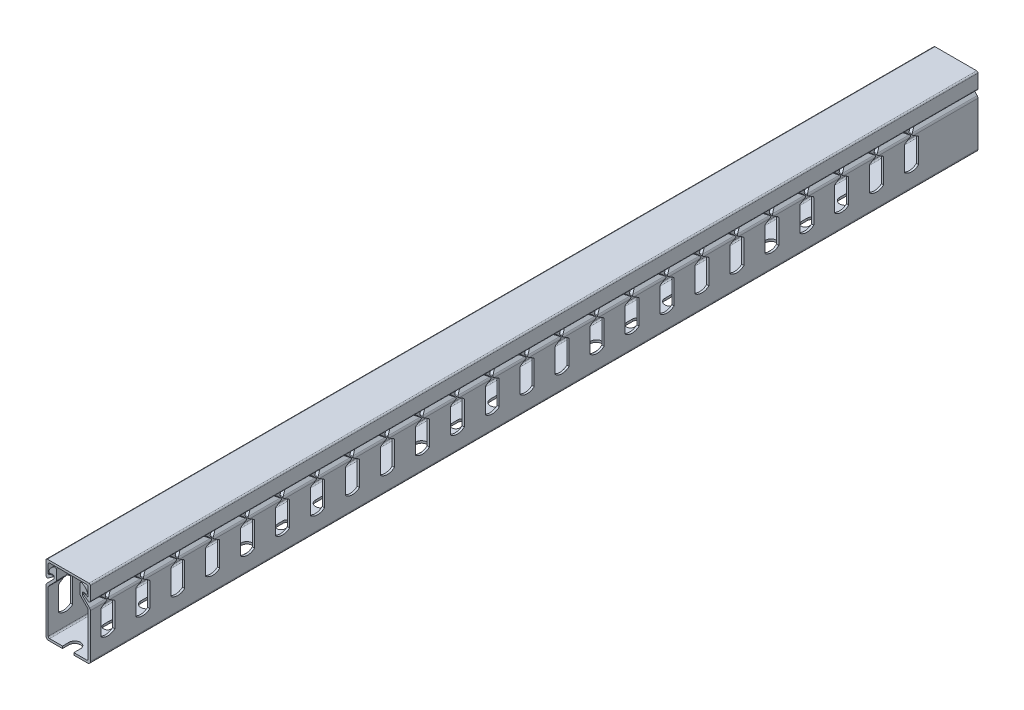
SolidWorks part; units mm, degrees
ref_plane "Front Plane" through (0, 0, 0) normal (0, 0, 1) x (1, 0, 0)
ref_plane "Top Plane" through (0, 0, 0) normal (0, 1, 0) x (1, 0, 0)
ref_plane "Right Plane" through (0, 0, 0) normal (1, 0, 0) x (0, 0, -1)
sketch "Sketch1" plane through (0, 0, 0) normal (0, 0, 1) x (1, 0, 0)
  line L0 (-12.7, 10.6985) -> (12.7, 10.6985) construction
  line L1 (12.7, -20) -> (-12.7, -20) construction
  line L2 (12.7, -20) -> (12.7, 20) construction
  line L3 (12.7, 20) -> (-12.7, 20) construction
  line L4 (-12.7, -20) -> (-12.7, 20) construction
  line L5 (0, 20) -> (0, -20) construction
  line L6 (12.7, 0) -> (-12.7, 0) construction
  line L7 (-12.7, 13.7872) -> (12.7, 13.7872) construction
  line L8 (6.8085, 20) -> (6.8085, 10.6985) construction
  line L9 (-6.8085, 20) -> (6.8085, 10.6985) construction
  line L10 (-6.8085, 20) -> (-6.8085, 10.6985) construction
  line L11 (-12.7, 18.222) -> (12.7, 18.222) construction
  line L12 (-12.7, 13.6284) -> (12.7, 13.6284) construction
  line L13 (-11.4341, 10.8542) -> (-7.685, 13.6284) construction
  line L14 (-10.1877, 13.798) -> (-6.8085, 14.3635) construction
  line L15 (12.7, 7.4) -> (6.8085, 13.4162) construction
  circle A0 centre (-11.9062, 11.4923) radius 0.7938 construction
  circle A1 centre (-10.3187, 14.5809) radius 0.7937 construction
  circle A2 centre (-7.6022, 17.4283) radius 0.7938 construction
  arc A3 (-7.9835, 18.1244) -> (-11.0321, 14.929) centre (-4.4831, 11.7329) ccw construction
  point P0 (0, 0)
  point P4 (11.43, 0)
  point P13 (0, 15.3493)
  point P16 (-11.1125, 13.7872)
  point P21 (-11.1125, 11.4923)
  point P26 (-10.3188, 13.7872)
  point P27 (-10.3188, 13.7872)
  point P28 (-11.1125, 14.5809)
  point P36 (12.7, 7.4)
  dimension "D6" = 7.2873
  dimension "Width" = 25.4
  dimension "Heigth" = 40
  dimension "Wall Thickness" = 1.27
  dimension "Cap Height" = 9.3015
  dimension "Lip Height" = 6.2128
  dimension "D1" = 13.6169
  dimension "D2" = 1.778
  dimension "Lip From Edge" = 1.5875
  dimension "D4" = 0.1588
  dimension "D5" = 36.5
  dimension "D3" = 80.5
  dimension "Shoulder Height" = 27.4
  dimension "D7" = 44.4
sketch "Sketch3" plane through (0, 0, 0) normal (1, 0, 0) x (0, 0, -1)
  line L0 (254, 0) -> (-254, 0) construction
  line L1 (-254, 20) -> (-254, -20) construction
  line L2 (-254, -20) -> (254, -20) construction
  line L3 (254, -20) -> (254, 20) construction
  line L4 (254, 20) -> (-254, 20) construction
  line L5 (-240, 20) -> (-240, 9.8437) construction
  line L6 (-240, 9.8437) -> (-243.873, 7.4) construction
  line L7 (-243.873, 7.4) -> (-244.127, 7.4) construction
  line L8 (-244.127, 7.4) -> (-248, 9.8437) construction
  line L9 (-248, 9.8437) -> (-248, 20) construction
  line L10 (-244.127, 7.4) -> (-248, 4.9563) construction
  line L11 (-248, 4.9563) -> (-248, -9.1796) construction
  line L12 (-248, -9.1796) -> (-240, -9.1796) construction
  line L13 (-240, -9.1796) -> (-240, 4.9563) construction
  line L14 (-243.873, 7.4) -> (-240, 4.9563) construction
  line L15 (-244, 7.4) -> (-244, -9.1796) construction
  line L16 (-244, 7.4) -> (-244, 20) construction
  line L17 (-248, 4.9563) -> (-240, 4.9563) construction
  line L18 (0, 7.4) -> (-243.873, 7.4) construction
  line L19 (-248, 9.8437) -> (-248, 4.9563) construction
  line L20 (-244.127, 7.4) -> (-248, 7.4) construction
  line L21 (-240, 4.9563) -> (-228, 4.9563) construction
  line L22 (-228, 4.9563) -> (-220, 4.9563) construction
  line L23 (-224, 4.9563) -> (-224, -9.1796) construction
  line L24 (-127, 20) -> (-127, -20) construction
  line L25 (127, 20) -> (127, -20) construction
  arc A0 (-248, -9.1796) -> (-240, -9.1796) centre (-244, -4.7075) ccw construction
  circle A1 centre (-244.8707, 7.4) radius 0.3969 construction
  circle A2 centre (-243.1293, 7.4) radius 0.3969 construction
  point P29 (-220, 4.9563)
  point P30 (-228, 4.9563)
  point P31 (-228, 4.9563)
  point P32 (-224, 4.9563)
  point P34 (-127, 0)
  point P39 (127, 0)
  dimension "D2" = 6
  dimension "D6" = 0.7937
  dimension "Length" = 508
  dimension "Side Cut Out Width" = 8
  dimension "D3" = 6
  dimension "D1" = 10.8204
  dimension "D4" = 64.5
  dimension "D5" = 0.254
  dimension "Cut Spacing" = 12
  dimension "Cut Center To Center" = 20
  dimension "D7" = 127
  dimension "D8" = 127
sketch "Sketch4" plane through (0, 0, 0) normal (0, 1, 0) x (1, 0, 0)
  line L0 (0, -257.75) -> (0, -250.25) construction
  line L1 (-12.7, 254) -> (12.7, 254) construction
  line L2 (-12.7, 254) -> (-12.7, -254) construction
  line L3 (-12.7, -254) -> (12.7, -254) construction
  line L4 (12.7, 254) -> (12.7, -254) construction
  line L5 (0, -254) -> (0, 254) construction
  line L6 (-12.7, 0) -> (12.7, 0) construction
  line L7 (-3.25, -257.75) -> (-3.25, -250.25) construction
  line L8 (3.25, -257.75) -> (3.25, -250.25) construction
  line L9 (0, -231.5) -> (0, -228) construction
  line L10 (-2.25, -231.5) -> (-2.25, -228) construction
  line L11 (2.25, -231.5) -> (2.25, -228) construction
  line L12 (0, -209.25) -> (0, -201.75) construction
  line L13 (-3.25, -209.25) -> (-3.25, -201.75) construction
  line L14 (3.25, -209.25) -> (3.25, -201.75) construction
  line L15 (0, -178.75) -> (0, -182.25) construction
  line L16 (2.25, -178.75) -> (2.25, -182.25) construction
  line L17 (-2.25, -178.75) -> (-2.25, -182.25) construction
  line L18 (-12.7, -127) -> (12.7, -127) construction
  line L19 (-12.7, 127) -> (12.7, 127) construction
  arc A0 (-3.25, -257.75) -> (3.25, -257.75) centre (0, -257.75) ccw construction
  arc A1 (3.25, -250.25) -> (-3.25, -250.25) centre (0, -250.25) ccw construction
  arc A2 (-2.25, -231.5) -> (2.25, -231.5) centre (0, -231.5) ccw construction
  arc A3 (2.25, -228) -> (-2.25, -228) centre (0, -228) ccw construction
  arc A4 (-3.25, -209.25) -> (3.25, -209.25) centre (0, -209.25) ccw construction
  arc A5 (3.25, -201.75) -> (-3.25, -201.75) centre (0, -201.75) ccw construction
  arc A6 (2.25, -178.75) -> (-2.25, -178.75) centre (0, -178.75) ccw construction
  arc A7 (-2.25, -182.25) -> (2.25, -182.25) centre (0, -182.25) ccw construction
  point P0 (0, 0)
  point P5 (0, -254)
  point P13 (0, -229.75)
  point P18 (0, -225.75)
  point P19 (0, -233.75)
  point P20 (0, -247)
  point P21 (0, -261)
  point P24 (0, -205.5)
  point P31 (0, -180.5)
  point P40 (0, -212.5)
  point P41 (0, -198.5)
  dimension "Large Hole Radius" = 3.25
  dimension "Large Hole Length" = 14
  dimension "Slot With" = 8
  dimension "End Hole Spacing" = 48.5
  dimension "D4" = 24.25
  dimension "Hole Spacing" = 25
  dimension "Mounting Hole Diameter" = 4.5
sketch "Sketch5" plane through (0, 0, 0) normal (0, 0, 1) x (1, 0, 0)
  line L0 (-6.8085, 17.4283) -> (-6.8085, 11.6011)
  line L1 (-6.8085, 20) -> (-6.8085, 10.6985) construction
  line L2 (-6.8085, 11.6011) -> (-11.43, 6.8817)
  line L3 (-11.43, 6.8817) -> (-11.43, -18.73)
  line L4 (-11.43, -18.73) -> (11.43, -18.73)
  line L5 (11.43, -18.73) -> (11.43, 6.8817)
  line L6 (11.43, 6.8817) -> (6.8085, 11.6011)
  line L7 (6.8085, 11.6011) -> (6.8085, 17.4283)
  line L8 (6.8085, 20) -> (6.8085, 10.6985) construction
  line L9 (12.7, 7.4) -> (6.8085, 13.4162) construction
  line L10 (0, 20) -> (0, -20) construction
  line L11 (11.43, 0) -> (12.7, 0) construction
  line L12 (8.0785, 12.1194) -> (6.8085, 12.1194) construction
  line L13 (-10.1877, 13.798) -> (-6.8085, 14.3635) construction
  line L14 (-10.1877, 13.798) -> (-8.0785, 14.151)
  line L15 (-8.0785, 14.151) -> (-8.0785, 12.1194)
  line L16 (-8.0785, 12.1194) -> (-12.7, 7.4)
  line L17 (-12.7, -20) -> (-12.7, 20) construction
  line L18 (-12.7, 7.4) -> (-12.7, -20)
  line L19 (-12.7, -20) -> (12.7, -20)
  line L20 (12.7, -20) -> (12.7, 7.4)
  line L21 (12.7, 7.4) -> (8.0785, 12.1194)
  line L22 (8.0785, 12.1194) -> (8.0785, 14.151)
  line L23 (6.8085, 12.1194) -> (-6.8085, 12.1194) construction
  line L24 (-6.8085, 12.1194) -> (-8.0785, 12.1194) construction
  line L25 (11.43, 6.8817) -> (12.3374, 7.7703) construction
  line L26 (-12.7, 18.222) -> (12.7, 18.222) construction
  line L27 (10.1877, 13.798) -> (8.0785, 14.151)
  line L28 (11.43, -18.73) -> (11.43, -20) construction
  line L29 (-12.7, 20) -> (-12.7, 11.4923)
  line L30 (-12.7, 20) -> (12.7, 20)
  line L31 (-11.4341, 10.8542) -> (-8.7512, 12.8395)
  line L32 (-11.4341, 10.8542) -> (-7.685, 13.6284) construction
  line L33 (12.7, 20) -> (12.7, 11.4923)
  line L34 (12.7, -20) -> (12.7, 20) construction
  line L35 (8.7512, 12.8395) -> (11.4341, 10.8542)
  line L36 (-12.7, 10.6985) -> (12.7, 10.6985) construction
  line L37 (-11.43, 12.4371) -> (-11.43, 18.73)
  line L38 (-11.43, 18.73) -> (11.43, 18.73)
  line L39 (11.43, 18.73) -> (11.43, 12.4371)
  line L40 (-11.43, 18.73) -> (-11.43, 20) construction
  line L41 (-11.43, 18.73) -> (-12.7, 18.73) construction
  line L42 (-11.43, 12.4371) -> (-10.6707, 12.999)
  line L43 (-11.0503, 12.7181) -> (-10.2949, 11.6972) construction
  line L44 (-8.9869, 13.5542) -> (-8.9869, 13.158) construction
  line L45 (10.6707, 12.999) -> (11.43, 12.4371)
  line L46 (10.6707, 12.999) -> (9.9153, 11.9781) construction
  circle A0 centre (-7.6022, 17.4283) radius 0.7938 construction
  arc A1 (-7.9835, 18.1244) -> (-11.0321, 14.929) centre (-4.4831, 11.7329) ccw construction
  arc A2 (-7.9835, 18.1244) -> (-11.0321, 14.929) centre (-4.4831, 11.7329) ccw
  circle A3 centre (-10.3187, 14.5809) radius 0.7937 construction
  arc A4 (-11.0321, 14.929) -> (-10.1877, 13.798) centre (-10.3187, 14.5809) ccw
  arc A5 (-6.8085, 17.4283) -> (-7.9835, 18.1244) centre (-7.6022, 17.4283) ccw
  arc A6 (7.9835, 18.1244) -> (6.8085, 17.4283) centre (7.6022, 17.4282) ccw
  arc A7 (10.1877, 13.798) -> (11.0321, 14.929) centre (10.3187, 14.5809) ccw
  arc A8 (7.9835, 18.1244) -> (11.0321, 14.929) centre (4.4831, 11.7329) cw
  circle A9 centre (-11.9062, 11.4923) radius 0.7938 construction
  arc A10 (-12.7, 11.4923) -> (-11.4341, 10.8542) centre (-11.9062, 11.4923) ccw
  arc A11 (11.4341, 10.8542) -> (12.7, 11.4923) centre (11.9062, 11.4923) ccw
  arc A12 (-8.7512, 12.8395) -> (-8.9869, 13.5542) centre (-8.9869, 13.158) ccw
  arc A13 (-10.6707, 12.999) -> (-8.9869, 13.5542) centre (-8.9869, 10.7234) cw
  arc A14 (8.7512, 12.8395) -> (8.9869, 13.5542) centre (8.9869, 13.158) cw
  arc A15 (8.9869, 13.5542) -> (10.6707, 12.999) centre (8.9869, 10.7234) cw
  point P10 (0, -18.73)
  point P81 (0, 18.73)
  dimension "D2" = 0.3962
  dimension "D1" = 3.3376
extrude "Boss-Extrude1" add sketch "Sketch5" along normal up to vertex (254 mm away) and the other way up to vertex (254 mm away) up to point (0, -20, 254) other way up to point (0, -20, -254)
fillet "Fillet1" radius 0.254 2 edges at (-11.43, 12.4371, 0) (11.43, 12.4371, 0)
fillet "Fillet2" radius 0.7937 4 edges at (12.7, 20, 0) (11.43, 18.73, 0) (-11.43, 18.73, 0) (-12.7, 20, 0)
fillet "Fillet3" radius 1.5875 4 edges at (-12.7, -20, 0) (12.7, -20, 0) (12.7, 7.4, 0) (-12.7, 7.4, 0)
fillet "Fillet4" radius 0.7937 8 edges at (-11.43, -18.73, 0) (11.43, -18.73, 0) (8.0785, 14.151, 0) (-8.0785, 14.151, 0) (-11.43, 6.8817, 0) (-6.8085, 11.6011, 0) (6.8085, 11.6011, 0) (11.43, 6.8817, 0)
sketch "Sketch6" plane through (0, 0, 0) normal (1, 0, 0) x (0, 0, -1)
  line L0 (-248, 20) -> (-248, 10.2814)
  line L1 (-248, 4.9563) -> (-248, -9.1796) construction
  line L2 (-244.127, 7.4) -> (-248, 4.9563) construction
  line L3 (-240, -9.1796) -> (-240, 4.9563) construction
  line L4 (-243.873, 7.4) -> (-240, 4.9563) construction
  line L5 (-240, 9.8437) -> (-243.873, 7.4) construction
  line L6 (-240, 20) -> (-240, 9.8437) construction
  line L7 (-244.127, 7.4) -> (-248, 9.8437) construction
  line L8 (-248, 4.5186) -> (-248, -9.1796)
  line L9 (-244.659, 7.0644) -> (-247.6298, 5.1899)
  line L10 (-240, -9.1796) -> (-240, 4.5186)
  line L11 (-243.341, 7.0644) -> (-240.3702, 5.1899)
  line L12 (-240.3702, 9.6101) -> (-243.341, 7.7356)
  line L13 (-240, 20) -> (-240, 10.2814)
  line L14 (-244.659, 7.7356) -> (-247.6298, 9.6101)
  line L15 (-240, 20) -> (-248, 20)
  circle A0 centre (-243.1293, 7.4) radius 0.3969 construction
  circle A1 centre (-244.8707, 7.4) radius 0.3969 construction
  arc A2 (-243.341, 7.7356) -> (-243.341, 7.0644) centre (-243.1293, 7.4) ccw
  arc A3 (-244.659, 7.0644) -> (-244.659, 7.7356) centre (-244.8707, 7.4) ccw
  arc A4 (-248, -9.1796) -> (-240, -9.1796) centre (-244, -4.7075) ccw construction
  arc A5 (-248, -9.1796) -> (-240, -9.1796) centre (-244, -4.7075) ccw
  arc A6 (-240.3702, 9.6101) -> (-240, 10.2814) centre (-240.7937, 10.2814) ccw
  arc A7 (-240, 4.5186) -> (-240.3702, 5.1899) centre (-240.7938, 4.5186) ccw
  arc A8 (-248, 4.5186) -> (-247.6298, 5.1899) centre (-247.2062, 4.5186) cw
  arc A9 (-248, 10.2814) -> (-247.6298, 9.6101) centre (-247.2062, 10.2814) ccw
  dimension "D1" = 0.7937
extrude "Cut-Extrude2" cut sketch "Sketch6" against normal through all both and the other way through all
pattern_linear "LPattern2" count 24 spacing 20 along (0, 0, -1) of "Cut-Extrude2"
sketch "Sketch7" plane through (0, -20, 0) normal (0, -1, 0) x (1, 0, 0)
  line L0 (-3.25, 257.75) -> (-3.25, 250.25) construction
  line L1 (3.25, 257.75) -> (3.25, 250.25) construction
  line L2 (-3.25, 257.75) -> (-3.25, 250.25)
  line L3 (3.25, 257.75) -> (3.25, 250.25)
  line L4 (-2.25, 231.5) -> (-2.25, 228) construction
  line L5 (2.25, 231.5) -> (2.25, 228) construction
  line L6 (-2.25, 231.5) -> (-2.25, 228)
  line L7 (2.25, 231.5) -> (2.25, 228)
  arc A0 (3.25, 257.75) -> (-3.25, 257.75) centre (0, 257.75) ccw construction
  arc A1 (-3.25, 250.25) -> (3.25, 250.25) centre (0, 250.25) ccw construction
  arc A2 (3.25, 257.75) -> (-3.25, 257.75) centre (0, 257.75) ccw
  arc A3 (-3.25, 250.25) -> (3.25, 250.25) centre (0, 250.25) ccw
  arc A4 (2.25, 231.5) -> (-2.25, 231.5) centre (0, 231.5) ccw construction
  arc A5 (-2.25, 228) -> (2.25, 228) centre (0, 228) ccw construction
  arc A6 (2.25, 231.5) -> (-2.25, 231.5) centre (0, 231.5) ccw
  arc A7 (-2.25, 228) -> (2.25, 228) centre (0, 228) ccw
extrude "Cut-Extrude3" cut sketch "Sketch7" against normal up to vertex (1.27 mm away) up to point (10.6363, -18.73, 254)
sketch "Sketch8" plane through (0, -20, 0) normal (0, -1, 0) x (1, 0, 0)
  line L0 (-2.25, 178.75) -> (-2.25, 182.25) construction
  line L1 (2.25, 178.75) -> (2.25, 182.25) construction
  line L2 (3.25, 209.25) -> (3.25, 201.75) construction
  line L3 (-3.25, 209.25) -> (-3.25, 201.75) construction
  line L4 (-2.25, 178.75) -> (-2.25, 182.25)
  line L5 (2.25, 178.75) -> (2.25, 182.25)
  line L6 (3.25, 209.25) -> (3.25, 201.75)
  line L7 (-3.25, 209.25) -> (-3.25, 201.75)
  arc A0 (-2.25, 178.75) -> (2.25, 178.75) centre (0, 178.75) ccw construction
  arc A1 (2.25, 182.25) -> (-2.25, 182.25) centre (0, 182.25) ccw construction
  arc A2 (3.25, 209.25) -> (-3.25, 209.25) centre (0, 209.25) ccw construction
  arc A3 (-3.25, 201.75) -> (3.25, 201.75) centre (0, 201.75) ccw construction
  arc A4 (-2.25, 178.75) -> (2.25, 178.75) centre (0, 178.75) ccw
  arc A5 (2.25, 182.25) -> (-2.25, 182.25) centre (0, 182.25) ccw
  arc A6 (3.25, 209.25) -> (-3.25, 209.25) centre (0, 209.25) ccw
  arc A7 (-3.25, 201.75) -> (3.25, 201.75) centre (0, 201.75) ccw
extrude "Cut-Extrude4" cut sketch "Sketch8" against normal up to vertex (1.27 mm away) up to point (-3.25, -18.73, 254)
pattern_linear "LPattern3" count 11 spacing 50 along (0, 0, -1) of "Cut-Extrude4"
equation "\"D2@Sketch1\"=\"Wall Thickness@Sketch1\"*1.4"
equation "\"D4@Sketch1\"=\"Wall Thickness@Sketch1\"*.125"
equation "\"D2@Sketch3\" = \"Side Cut Out Width@Sketch3\" * .75"
equation "\"D4@Sketch4\" = \"End Hole Spacing@Sketch4\" / 2"
equation "\"D3@LPattern2\"=\"Cut Center To Center@Sketch3\""
equation "\"D1@LPattern2\"=\"Length@Sketch3\"/\"Cut Center To Center@Sketch3\"-1"
equation "\"D1@LPattern3\"=(\"Length@Sketch3\"/50mm)+1"
equation "\"D7@Sketch3\"=\"D8@Sketch3\""
